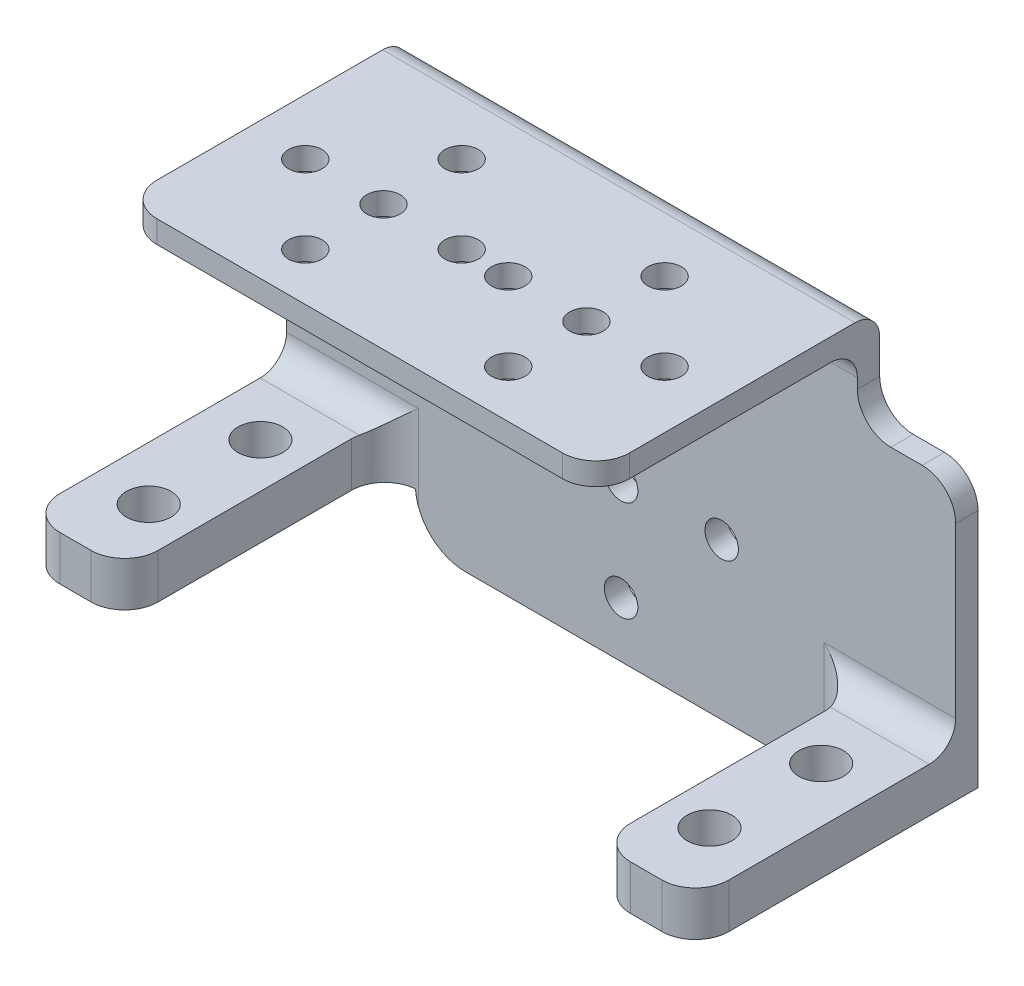
SolidWorks part; units mm, degrees
ref_plane "前视基准面" through (0, 0, 0) normal (0, 0, 1) x (1, 0, 0)
ref_plane "上视基准面" through (0, 0, 0) normal (0, 1, 0) x (1, 0, 0)
ref_plane "右视基准面" through (0, 0, 0) normal (1, 0, 0) x (0, 0, -1)
sketch "Sketch1" plane through (0, 0, 0) normal (0, 0, 1) x (1, 0, 0)
  line L0 (-21.15, 16.48) -> (21.15, 16.48)
  line L1 (-21.15, 18.48) -> (21.15, 18.48)
  line L2 (-21.15, 18.48) -> (-21.15, -14.28)
  line L3 (-4.3498, -18.48) -> (13.96, -18.48)
  line L4 (21.15, 18.48) -> (21.15, -14.28)
  line L5 (-13.96, -18.48) -> (-4.3498, -18.48)
  line L6 (-18.4, -9.12) -> (18.4, -9.12)
  line L7 (-18.4, -9.12) -> (-18.4, -14.04)
  line L8 (-13.96, -18.48) -> (13.96, -18.48)
  line L9 (18.4, -9.12) -> (18.4, -14.04)
  line L10 (-4.3498, -18.48) -> (13.96, -18.48)
  line L11 (-21.15, -14.28) -> (-18.3935, -14.28)
  line L12 (21.15, 10.22) -> (29.95, 10.22)
  line L13 (21.15, 10.22) -> (21.15, -14.28)
  line L14 (21.15, -14.28) -> (29.95, -14.28)
  line L15 (29.95, 10.22) -> (29.95, -14.28)
  line L16 (-29.95, 10.22) -> (-21.15, 10.22)
  line L17 (-29.95, 10.22) -> (-29.95, -14.28)
  line L18 (-29.95, -14.28) -> (-21.15, -14.28)
  line L19 (-21.15, 10.22) -> (-21.15, -14.28)
  line L23 (21.15, -14.28) -> (18.3935, -14.28)
  line L24 (21.15, -10.28) -> (29.95, -10.28)
  line L25 (21.15, -10.28) -> (21.15, -14.28)
  line L26 (21.15, -14.28) -> (29.95, -14.28)
  line L27 (29.95, -10.28) -> (29.95, -14.28)
  line L28 (-29.95, -10.28) -> (-21.15, -10.28)
  line L29 (-29.95, -10.28) -> (-29.95, -14.28)
  line L30 (-29.95, -14.28) -> (-21.15, -14.28)
  line L31 (-21.15, -10.28) -> (-21.15, -14.28)
  arc A0 (-13.96, -18.48) -> (-18.4, -14.04) centre (-13.96, -14.04) cw
  arc A1 (13.96, -18.48) -> (18.4, -14.04) centre (13.96, -14.04) ccw
  point P20 (18.4, -18.48)
  point P30 (-25.55, -14.28)
  point P32 (-25.55, -10.28)
  dimension "D9" = 4.44
  dimension "D10" = 4.44
  dimension "D2" = 42.3
  dimension "D3" = 21.15
  dimension "D4" = 18.48
  dimension "D5" = 2
  dimension "D6" = 9.36
  dimension "D7" = 36.8
  dimension "D8" = 18.4
  dimension "D11" = 18.48
  dimension "D12" = 24.5
  dimension "D13" = 24.5
  dimension "D14" = 8.8
  dimension "D15" = 8.8
  dimension "D16" = 32.76
  dimension "D18" = 4
  dimension "D19" = 4
extrude "Boss-Extrude1" add sketch "Sketch1" along normal blind 2 contours L6 L4 L0 L2 | L3 A1 L9 L6 L7 A0 L5 | L17 L28 L19 L2 L16 | L4 L24 L15 L12 region at (0, 3.2872, 0) region at (-25.55, -0.03, 0) region at (25.55, -0.03, 0) region at (0, -13.7071, 0)
extrude "Boss-Extrude2" add sketch "Sketch1<3>" along normal blind 25.4 contours L4 L1 L2 L0 region at (0, 17.48, 0)
sketch "Sketch1<3>" plane through (0, 0, 0) normal (0, 0, 1) x (1, 0, 0) same geometry as "Sketch1"
extrude "Boss-Extrude3" add sketch "Sketch1<4>" along normal blind 25.3 contours L28 L17 L18 L2 | L24 L13 L14 L15 region at (-25.55, -12.28, 0) region at (25.55, -12.28, 0)
sketch "Sketch1<4>" plane through (0, 0, 0) normal (0, 0, 1) x (1, 0, 0) same geometry as "Sketch1"
fillet "Fillet31" radius 3 10 edges at (21.15, -12.28, 25.3) (29.95, -12.28, 25.3) (21.15, 17.48, 25.4) (-21.15, 17.48, 25.4) (-29.95, -12.28, 25.3) (-21.15, -12.28, 25.3) (-29.95, 10.22, 1) (-21.15, 10.22, 1) (21.15, 10.22, 1) (29.95, 10.22, 1)
fillet "Fillet32" radius 2.36 3 edges at (25.55, -10.28, 2) (-25.55, -10.28, 2) (0, 16.48, 2)
sketch "Sketch2" plane through (0, -14.28, 0) normal (0, -1, 0) x (1, 0, 0)
  line L0 (24.15, 25.3) -> (26.95, 25.3) construction
  line L1 (25.05, 19.14) -> (25.05, 9.14) construction
  line L2 (21.15, 22.3) -> (21.15, 2) construction
  line L3 (-26.95, 25.3) -> (-24.15, 25.3) construction
  line L5 (-21.15, 22.3) -> (-21.15, 2) construction
  circle A0 centre (25.05, 19.14) radius 2
  circle A1 centre (25.05, 9.14) radius 2
  circle A2 centre (-25.15, 19.14) radius 2
  circle A3 centre (-25.15, 9.14) radius 2
  dimension "D1" = 4
  dimension "D2" = 4
  dimension "D7" = 4
  dimension "D8" = 4
  dimension "D3" = 6.16
  dimension "D4" = 10
  dimension "D5" = 3.9
  dimension "D9" = 6.16
  dimension "D10" = 4
  dimension "D11" = 10
fillet "Fillet26" radius 2.2 1 edges at (0, 18.48, 0) type face fillet first side face at (0, 1.4296, 0) second side face at (0, 18.48, 16.1404)
fillet "Fillet28" [suppressed] radius 0.5
fillet "Fillet29" [suppressed] radius 0.5
fillet "Fillet30" [suppressed] radius 1
extrude "Cut-Extrude1" cut sketch "Sketch2" against normal mid plane 20
sketch "Sketch3" plane through (0, 18.48, 0) normal (0, 1, 0) x (1, 0, 0)
  line L0 (21.15, -2.2) -> (-21.15, -2.2) construction
  line L1 (-21.15, -22.4) -> (-21.15, -2.2) construction
  line L2 (-18.15, -25.4) -> (18.15, -25.4) construction
  line L3 (21.15, -22.4) -> (21.15, -2.2) construction
  line L4 (0, -34.8199) -> (0, 24.3344) construction
  circle A5 centre (-9.1346, -14.14) radius 1.5
  circle A6 centre (-9.1346, -7.14) radius 1.5
  circle A7 centre (-2.1346, -14.14) radius 1.5
  circle A8 centre (-9.1346, -21.14) radius 1.5
  circle A9 centre (-16.1346, -14.14) radius 1.5
  circle A10 centre (9.0346, -14.14) radius 1.5
  circle A11 centre (9.0346, -7.14) radius 1.5
  circle A12 centre (16.0346, -14.14) radius 1.5
  circle A13 centre (9.0346, -21.14) radius 1.5
  circle A14 centre (2.0346, -14.14) radius 1.5
  point P31 (-9.1346, -14.14)
  point P34 (9.0346, -14.14)
  point P43 (9.0346, -14.14)
  dimension "D2" = 7
  dimension "D7" = 3
  dimension "D8" = 3
  dimension "D3" = 3
  dimension "D4" = 3
  dimension "D5" = 4
  dimension "D6" = 12.0154
  dimension "D10" = 4.94
  dimension "D11" = 23.2
  dimension "D12" = 42.3
  dimension "D9" = 4
extrude "Cut-Extrude2" cut sketch "Sketch3" against normal blind 10
sketch "Sketch4" plane through (0, 0, 0) normal (0, 0, -1) x (-1, 0, 0)
  line L3 (18.4, -9.12) -> (21.15, -9.12)
  line L4 (-21.15, 18.48) -> (21.15, 18.48) construction
  line L5 (-21.15, 18.48) -> (21.15, 18.48)
  circle A0 centre (0, 4.48) radius 1.5
  circle A1 centre (0, -4.52) radius 1.5
  circle A2 centre (0, -13.52) radius 1.5
  circle A3 centre (9, -4.52) radius 1.5
  circle A4 centre (-9, -4.52) radius 1.5
  dimension "D1" = 3
  dimension "D2" = 3
  dimension "D4" = 3
  dimension "D6" = 3
  dimension "D8" = 3
  dimension "D3" = 9
  dimension "D5" = 9
  dimension "D7" = 9
  dimension "D9" = 9
  dimension "D10" = 23
extrude "Cut-Extrude3" cut sketch "Sketch4" against normal blind 10 contours A4 | A0 | A3 | A2 | A1 region at (0, 4.48, 0) region at (0, -13.52, 0) region at (-9, -4.52, 0) region at (9, -4.52, 0)
fillet "Fillet33" radius 3 2 edges at (21.15, -11.1, 2) (-21.15, -11.1, 2)
